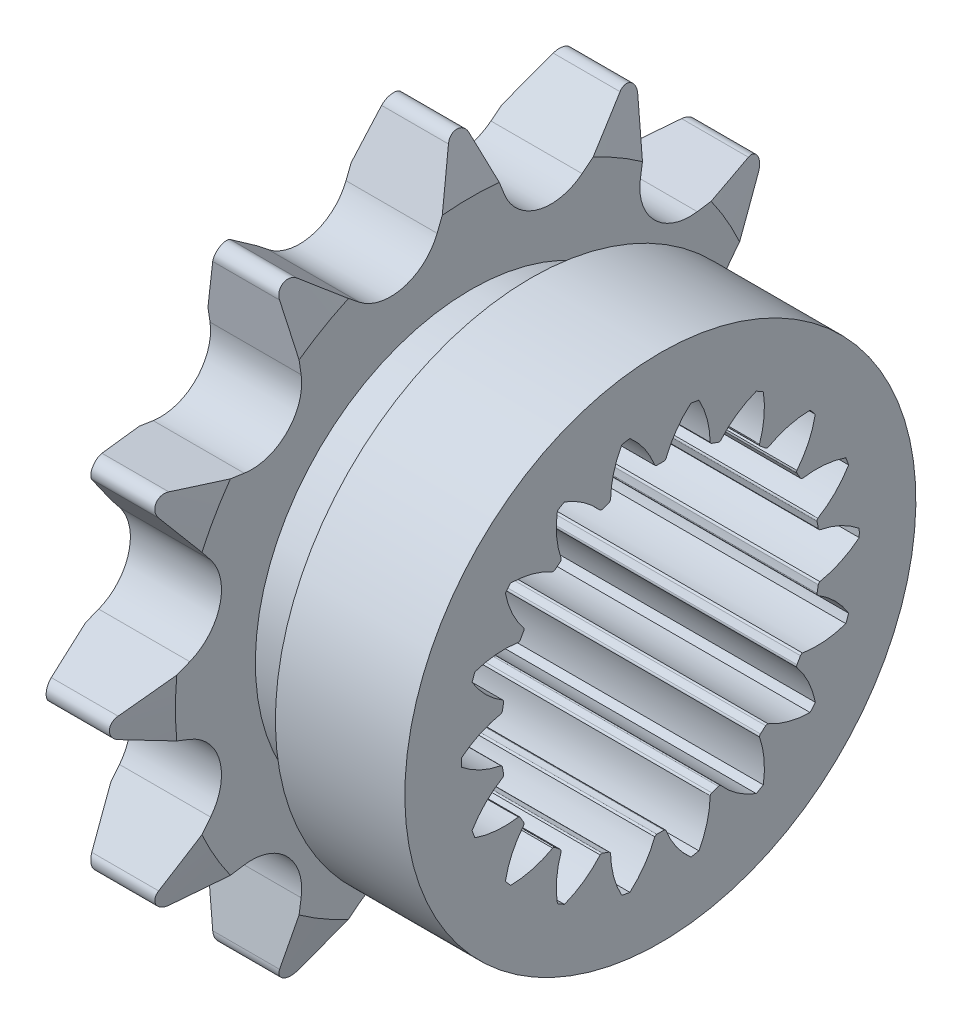
SolidWorks part; units mm, degrees
material "1144"
ref_plane "Front Plane" through (0, 0, 0) normal (0, 0, 1) x (1, 0, 0)
ref_plane "Top Plane" through (0, 0, 0) normal (0, 1, 0) x (1, 0, 0)
ref_plane "Right Plane" through (0, 0, 0) normal (1, 0, 0) x (0, 0, -1)
ref_axis "Axis1" through (-63.0158, 0, 0) along (1, 0, 0)
sketch "Sketch1" plane through (0, 0, 0) normal (0, 0, 1) x (1, 0, 0)
  line L0 (3.6068, 17.0561) -> (3.6068, 0) construction
  line L1 (22.225, 0) -> (22.225, 20.2311)
  line L3 (7.2136, 17.0561) -> (0, 17.0561)
  line L7 (0, 27.5082) -> (0, 30.0482) construction
  line L8 (0, 27.5082) -> (7.2136, 27.5082)
  line L9 (22.225, 0) -> (0, 0)
  line L10 (0, 0) -> (-84.1773, 0) construction
  line L11 (0, 17.0561) -> (0, 27.5082) construction
  line L12 (7.2136, 27.5082) -> (73.2462, 27.5082) construction
  line L13 (22.225, 0) -> (22.225, -20.2311) construction
  line L14 (3.6068, 0) -> (3.6068, -17.0561)
  line L15 (-15.4432, -17.0561) -> (22.6568, -17.0561)
  point P11 (0, 30.0482)
  dimension "D1" = 2.54
  dimension "hub_dia" = 40.4622
  dimension "width_teetth" = 7.2136
  dimension "D2" = 38.1
  dimension "length_thru" = 22.225
  dimension "OD" = 55.0164
  dimension "length_over_teeth" = 7.2136
  dimension "recess_hub_diam" = 34.1122
  dimension "hub_type" = 22.225
  dimension "projection 1" = 15.0114
  dimension "projection 2" = 0
sketch "Sketch2" plane through (0, 0, 0) normal (1, 0, 0) x (0, 0, -1)
  line L0 (0, 0) -> (0, 27.5082) construction
  line L1 (0, 0) -> (-13.7541, 23.8228) construction
  line L2 (0, 0) -> (-6.3502, 23.6991) construction
  line L3 (-0.8057, 26.9597) -> (-2.6638, 22.246)
  line L4 (-2.6638, 22.246) -> (-6.3502, 23.6991) construction
  line L5 (-0.8217, 27.4959) -> (0, 0) construction
  line L6 (-2.735, 27.3719) -> (0, 0) construction
  line L7 (-6.3502, 23.6991) -> (-2.4074, 24.0931) construction
  arc A1 (0, 27.5082) -> (-13.7541, 23.8228) centre (0, 0) ccw
  circle A2 centre (0, 0) radius 24.5351 construction
  circle A3 centre (-6.3502, 23.6991) radius 3.9624
  arc A4 (0, 27.5082) -> (-0.8057, 26.9597) centre (0, 26.6421) ccw
  dimension "pitch_diam" = 49.0703
  dimension "roller_diam" = 7.9248
  dimension "D1" = 1.712
  dimension "ang_1" = 30
  dimension "OD/2" = 27.5082
sketch "Taper Per Foot" plane through (0, 0, 0) normal (0, 0, 1) x (1, 0, 0)
  line L0 (22.225, 0) -> (22.225, 127)
  line L1 (22.225, 0) -> (22.225, 20.2311) construction
  line L2 (22.225, 127) -> (-282.575, 6.35)
  line L3 (-282.575, 6.35) -> (-282.575, 0)
  line L4 (-282.575, 0) -> (22.225, 0)
  line L5 (-282.575, 0) -> (-285.7823, 0) construction
  line L6 (-282.575, 6.35) -> (22.225, 6.35)
  line L7 (22.225, 6.35) -> (22.225, 127)
  dimension "1 Ft" = 304.8
  dimension "1 in" = 254
  dimension "Small End Diam" = 12.7
  dimension "Large End Diam" = 12.7
ref_plane "Plane1" through (7.2136, 0, 0) normal (1, 0, 0) x (0, 0, -1)
ref_plane "Plane2" through (7.2136, 0, 0) normal (1, 0, 0) x (0, 0, -1)
ref_plane "Plane3" through (0, 17.0561, 0) normal (-1, 0, 0) x (0, 0, 1)
ref_plane "Plane4" through (22.225, 0, 0) normal (1, 0, 0) x (0, 0, -1)
ref_plane "Plane5" through (3.6068, 0, 0) normal (1, 0, 0) x (0, 0, -1)
sketch "Sketch13" plane through (0, 0, 0) normal (0, 0, 1) x (1, 0, 0)
  line L0 (22.225, 0) -> (22.225, 20.2311) construction
  line L1 (0, 0) -> (22.225, 0)
  line L2 (0, 0) -> (0, 27.5082)
  line L3 (0, 27.5082) -> (22.225, 27.5082)
  line L4 (22.225, 0) -> (22.225, 27.5082)
revolve "Revolve1" add sketch "Sketch13" angle 360 about L10
sketch "Sketch6" plane through (0, -16.51, 0) normal (1, 0, 0) x (0, 0, -1)
  line L0 (-0.8057, 43.4697) -> (-2.6638, 38.756) construction
  line L1 (-0.8057, 43.4697) -> (-2.6638, 38.756)
  line L2 (-6.3502, 40.2091) -> (0, 16.51) construction
  line L3 (-12.7821, 40.2607) -> (-8.8161, 37.1075)
  arc A0 (0, 44.0182) -> (-0.8057, 43.4697) centre (0, 43.1521) ccw construction
  arc A1 (0, 44.0182) -> (-0.8057, 43.4697) centre (0, 43.1521) ccw
  arc A2 (-13.7541, 40.3328) -> (-12.7821, 40.2607) centre (-13.3211, 39.5828) cw
  arc A3 (-2.6638, 38.756) -> (-8.8161, 37.1075) centre (-6.3502, 40.2091) cw
  arc A4 (0, 44.0182) -> (-13.7541, 40.3328) centre (0, 16.51) ccw
extrude "Cut-Extrude1" cut sketch "Sketch6" along normal up to vertex (7.2136 mm away) up to point (7.2136, 17.0561, 0)
pattern_circular "CirPattern1" count 12 over 360 about axis through (-63.0158, 0, 0) along (1, 0, 0) of "Cut-Extrude1"
sketch "Sketch15" plane through (0, 0, 0) normal (0, 0, 1) x (1, 0, 0)
  line L1 (134.2136, 20.2311) -> (7.2136, 20.2311)
  line L2 (134.2136, 20.2311) -> (134.2136, 42.7482)
  line L3 (134.2136, 42.7482) -> (7.2136, 42.7482)
  line L4 (7.2136, 20.2311) -> (7.2136, 42.7482)
  line L5 (3.6068, 216.4797) -> (3.6068, 17.0561) construction
  line L6 (-127, 20.2311) -> (0, 20.2311)
  line L7 (0, 20.2311) -> (0, 42.7482)
  line L8 (-127, 42.7482) -> (0, 42.7482)
  line L9 (-127, 20.2311) -> (-127, 42.7482)
  dimension "D1" = 12.7
  dimension "D2" = 127
revolve "hub Cut-Revolve3" cut sketch "Sketch15" angle 360 about L10
sketch "Sketch4" plane through (0, 0, 0) normal (0, 0, 1) x (1, 0, 0)
  line L0 (0, 27.5082) -> (1.1045, 27.5082)
  line L2 (1.1045, 27.5082) -> (0, 23.3861)
  line L4 (0, 23.3861) -> (0, 27.5082)
  line L5 (3.6068, 27.5082) -> (3.6068, 44.9612) construction
  line L6 (7.2136, 27.5082) -> (6.1091, 27.5082)
  line L7 (7.2136, 23.3861) -> (7.2136, 27.5082)
  line L8 (6.1091, 27.5082) -> (7.2136, 23.3861)
  line L9 (0, 0) -> (-52.1231, 0) construction
  line L10 (0, 0) -> (-84.1773, 0) construction
  line L17 (0, 27.5082) -> (7.2136, 27.5082) construction
  dimension "D1" = 15
  dimension "D2" = 4.1221
revolve "Teeth Chamfer" cut sketch "Sketch4" angle 360 about L9
sketch "Sketch16" plane through (0, 0, 0) normal (0, 0, 1) x (1, 0, 0)
  line L1 (7.2136, 20.2311) -> (11.9761, 20.2311)
  line L2 (7.2136, 20.2311) -> (7.2136, 17.0561)
  line L3 (7.2136, 17.0561) -> (11.9761, 17.0561)
  line L4 (11.9761, 20.2311) -> (11.9761, 17.0561)
  line L5 (11.9761, 20.2311) -> (22.225, 20.2311) construction
  dimension "recess_width" = 4.7625
  dimension "recess_height" = 3.175
revolve "Recess" cut sketch "Sketch16" angle 360 about L10
sketch "Sketch32" plane through (22.225, 0, 0) normal (1, 0, 0) x (0, 0, -1)
  circle A1 centre (0, 0) radius 20.2311
  circle A2 centre (0, 0) radius 20.2311
  dimension "D1" = 0
extrude "Collar Reduction" [suppressed] cut sketch "Sketch32" against normal offset from surface (2.455 mm away) 19.77 up to face at (0, 0, 0)
ref_plane "Sprocket Teeth Center" through (3.6068, 0, 0) normal (-1, 0, 0) x (0, 0, 1)
sketch "Sketch35" plane through (3.6068, 0, 0) normal (1, 0, 0) x (0, 0, -1)
  circle A0 centre (0, 0) radius 24.5351 construction
  circle A1 centre (0, 0) radius 24.5351 construction
sketch "Sketch36" plane through (0, 0, 0) normal (-1, 0, 0) x (0, 0, 1)
  arc A34 (-7.5926, 13.7968) -> (-4.773, 11.8201) centre (-10.1337, 7.1728) cw
  arc A35 (-4.773, 11.8201) -> (-4.5847, 11.7902) centre (-4.6432, 12.0297) ccw
  arc A36 (-0.6644, 3.068) -> (-0.7894, 2.924) centre (-0.8986, 3.1451) cw
  arc A37 (-4.5847, 11.7902) -> (-4.0582, 11.9816) centre (0, 0) cw
  arc A38 (-8.1521, 13.4738) -> (-7.5639, 13.8125) centre (0, 0) cw
  arc A39 (-8.3407, 9.5111) -> (-7.9114, 9.8711) centre (0, 0) cw
  arc A40 (-7.85, 10.0436) -> (-7.9183, 9.8655) centre (-8.0965, 10.0359) cw
  arc A41 (-8.1521, 13.4738) -> (-7.85, 10.0436) centre (-1.145, 12.3625) ccw
  arc A42 (-2.4159, 15.5616) -> (-0.4424, 12.7398) centre (-7.0693, 10.2062) cw
  arc A43 (-0.4424, 12.7398) -> (-0.2757, 12.6472) centre (-0.2487, 12.8923) ccw
  arc A44 (-0.2757, 12.6472) -> (0.2845, 12.647) centre (0, 0) cw
  arc A45 (-3.0522, 15.4494) -> (-2.3836, 15.5666) centre (0, 0) cw
  arc A46 (-4.5847, 11.7902) -> (-4.0582, 11.9816) centre (0, 0) cw
  arc A47 (-3.9415, 12.1228) -> (-4.0666, 11.9788) centre (-4.1757, 12.1999) cw
  arc A48 (-3.0522, 15.4494) -> (-3.9415, 12.1228) centre (3.1523, 12.0085) ccw
  arc A49 (3.0522, 15.4494) -> (3.9415, 12.1228) centre (-3.1523, 12.0085) cw
  arc A50 (3.9415, 12.1228) -> (4.0666, 11.9788) centre (4.1757, 12.1999) ccw
  arc A51 (4.0666, 11.9788) -> (4.5929, 11.787) centre (0, 0) cw
  arc A52 (2.4159, 15.5616) -> (3.0842, 15.443) centre (0, 0) cw
  arc A53 (-0.2757, 12.6472) -> (0.2845, 12.647) centre (0, 0) cw
  arc A54 (0.4424, 12.7398) -> (0.2757, 12.6472) centre (0.2487, 12.8923) cw
  arc A55 (2.4159, 15.5616) -> (0.4424, 12.7398) centre (7.0693, 10.2062) ccw
  arc A56 (8.1521, 13.4738) -> (7.85, 10.0436) centre (1.145, 12.3625) cw
  arc A57 (7.85, 10.0436) -> (7.9183, 9.8655) centre (8.0965, 10.0359) ccw
  arc A58 (7.9183, 9.8655) -> (8.3473, 9.5053) centre (0, 0) cw
  arc A59 (7.5926, 13.7968) -> (8.18, 13.4568) centre (0, 0) cw
  arc A60 (4.0666, 11.9788) -> (4.5929, 11.787) centre (0, 0) cw
  arc A61 (4.773, 11.8201) -> (4.5847, 11.7902) centre (4.6432, 12.0297) cw
  arc A62 (7.5926, 13.7968) -> (4.773, 11.8201) centre (10.1337, 7.1728) ccw
  arc A63 (12.2688, 9.873) -> (10.8117, 6.753) centre (5.3042, 11.2253) cw
  arc A64 (10.8117, 6.753) -> (10.815, 6.5624) centre (11.0407, 6.6616) ccw
  arc A65 (10.815, 6.5624) -> (11.0949, 6.0771) centre (0, 0) cw
  arc A66 (11.8535, 10.368) -> (12.2892, 9.8476) centre (0, 0) cw
  arc A67 (7.9183, 9.8655) -> (8.3473, 9.5053) centre (0, 0) cw
  arc A68 (8.5279, 9.4748) -> (8.3407, 9.5111) centre (8.4775, 9.7162) cw
  arc A69 (11.8535, 10.368) -> (8.5279, 9.4748) centre (11.9758, 3.2743) ccw
  arc A70 (14.9057, 5.0814) -> (12.4694, 2.6479) centre (8.8236, 8.7342) cw
  arc A71 (12.4694, 2.6479) -> (12.4072, 2.4677) centre (12.6532, 2.4837) ccw
  arc A72 (12.4072, 2.4677) -> (12.5043, 1.916) centre (0, 0) cw
  arc A73 (14.6847, 5.6886) -> (14.9162, 5.0505) centre (0, 0) cw
  arc A74 (10.815, 6.5624) -> (11.0949, 6.0771) centre (0, 0) cw
  arc A75 (11.2542, 5.9867) -> (11.0907, 6.0849) centre (11.2894, 6.2307) cw
  arc A76 (14.6847, 5.6886) -> (11.2542, 5.9867) centre (12.3735, -1.0191) ccw
  arc A77 (15.7447, -0.3231) -> (12.623, -1.7765) centre (11.2787, 5.1896) cw
  arc A78 (12.623, -1.7765) -> (12.503, -1.9247) centre (12.7396, -1.9938) ccw
  arc A79 (12.503, -1.9247) -> (12.4055, -2.4763) centre (0, 0) cw
  arc A80 (15.7447, 0.3231) -> (15.744, -0.3557) centre (0, 0) cw
  arc A81 (12.4072, 2.4677) -> (12.5043, 1.916) centre (0, 0) cw
  arc A82 (12.623, 1.7765) -> (12.503, 1.9247) centre (12.7396, 1.9938) cw
  arc A83 (15.7447, 0.3231) -> (12.623, 1.7765) centre (11.2787, -5.1896) ccw
  arc A84 (14.6847, -5.6886) -> (11.2542, -5.9867) centre (12.3735, 1.0191) cw
  arc A85 (11.2542, -5.9867) -> (11.0907, -6.0849) centre (11.2894, -6.2307) ccw
  arc A86 (11.0907, -6.0849) -> (10.8104, -6.5699) centre (0, 0) cw
  arc A87 (14.9057, -5.0814) -> (14.6728, -5.719) centre (0, 0) cw
  arc A88 (12.503, -1.9247) -> (12.4055, -2.4763) centre (0, 0) cw
  arc A89 (12.4694, -2.6479) -> (12.4072, -2.4677) centre (12.6532, -2.4837) cw
  arc A90 (14.9057, -5.0814) -> (12.4694, -2.6479) centre (8.8236, -8.7342) ccw
  arc A91 (11.8535, -10.368) -> (8.5279, -9.4748) centre (11.9758, -3.2743) cw
  arc A92 (8.5279, -9.4748) -> (8.3407, -9.5111) centre (8.4775, -9.7162) ccw
  arc A93 (8.3407, -9.5111) -> (7.9114, -9.8711) centre (0, 0) cw
  arc A94 (12.2688, -9.873) -> (11.832, -10.3925) centre (0, 0) cw
  arc A95 (11.0907, -6.0849) -> (10.8104, -6.5699) centre (0, 0) cw
  arc A96 (10.8117, -6.753) -> (10.815, -6.5624) centre (11.0407, -6.6616) cw
  arc A97 (12.2688, -9.873) -> (10.8117, -6.753) centre (5.3042, -11.2253) ccw
  arc A98 (7.5926, -13.7968) -> (4.773, -11.8201) centre (10.1337, -7.1728) cw
  arc A99 (4.773, -11.8201) -> (4.5847, -11.7902) centre (4.6432, -12.0297) ccw
  arc A100 (4.5847, -11.7902) -> (4.0582, -11.9816) centre (0, 0) cw
  arc A101 (8.1521, -13.4738) -> (7.5639, -13.8125) centre (0, 0) cw
  arc A102 (8.3407, -9.5111) -> (7.9114, -9.8711) centre (0, 0) cw
  arc A103 (7.85, -10.0436) -> (7.9183, -9.8655) centre (8.0965, -10.0359) cw
  arc A104 (8.1521, -13.4738) -> (7.85, -10.0436) centre (1.145, -12.3625) ccw
  arc A105 (2.4159, -15.5616) -> (0.4424, -12.7398) centre (7.0693, -10.2062) cw
  arc A106 (0.4424, -12.7398) -> (0.2757, -12.6472) centre (0.2487, -12.8923) ccw
  arc A107 (0.2757, -12.6472) -> (-0.2845, -12.647) centre (0, 0) cw
  arc A108 (3.0522, -15.4494) -> (2.3836, -15.5666) centre (0, 0) cw
  arc A109 (4.5847, -11.7902) -> (4.0582, -11.9816) centre (0, 0) cw
  arc A110 (3.9415, -12.1228) -> (4.0666, -11.9788) centre (4.1757, -12.1999) cw
  arc A111 (3.0522, -15.4494) -> (3.9415, -12.1228) centre (-3.1523, -12.0085) ccw
  arc A112 (-3.0522, -15.4494) -> (-3.9415, -12.1228) centre (3.1523, -12.0085) cw
  arc A113 (-3.9415, -12.1228) -> (-4.0666, -11.9788) centre (-4.1757, -12.1999) ccw
  arc A114 (-4.0666, -11.9788) -> (-4.5929, -11.787) centre (0, 0) cw
  arc A115 (-2.4159, -15.5616) -> (-3.0842, -15.443) centre (0, 0) cw
  arc A116 (0.2757, -12.6472) -> (-0.2845, -12.647) centre (0, 0) cw
  arc A117 (-0.4424, -12.7398) -> (-0.2757, -12.6472) centre (-0.2487, -12.8923) cw
  arc A118 (-2.4159, -15.5616) -> (-0.4424, -12.7398) centre (-7.0693, -10.2062) ccw
  arc A119 (-8.1521, -13.4738) -> (-7.85, -10.0436) centre (-1.145, -12.3625) cw
  arc A120 (-7.85, -10.0436) -> (-7.9183, -9.8655) centre (-8.0965, -10.0359) ccw
  arc A121 (-7.9183, -9.8655) -> (-8.3473, -9.5053) centre (0, 0) cw
  arc A122 (-7.5926, -13.7968) -> (-8.18, -13.4568) centre (0, 0) cw
  arc A123 (-4.0666, -11.9788) -> (-4.5929, -11.787) centre (0, 0) cw
  arc A124 (-4.773, -11.8201) -> (-4.5847, -11.7902) centre (-4.6432, -12.0297) cw
  arc A125 (-7.5926, -13.7968) -> (-4.773, -11.8201) centre (-10.1337, -7.1728) ccw
  arc A126 (-12.2688, -9.873) -> (-10.8117, -6.753) centre (-5.3042, -11.2253) cw
  arc A127 (-10.8117, -6.753) -> (-10.815, -6.5624) centre (-11.0407, -6.6616) ccw
  arc A128 (-10.815, -6.5624) -> (-11.0949, -6.0771) centre (0, 0) cw
  arc A129 (-11.8535, -10.368) -> (-12.2892, -9.8476) centre (0, 0) cw
  arc A130 (-7.9183, -9.8655) -> (-8.3473, -9.5053) centre (0, 0) cw
  arc A131 (-8.5279, -9.4748) -> (-8.3407, -9.5111) centre (-8.4775, -9.7162) cw
  arc A132 (-11.8535, -10.368) -> (-8.5279, -9.4748) centre (-11.9758, -3.2743) ccw
  arc A133 (-14.9057, -5.0814) -> (-12.4694, -2.6479) centre (-8.8236, -8.7342) cw
  arc A134 (-12.4694, -2.6479) -> (-12.4072, -2.4677) centre (-12.6532, -2.4837) ccw
  arc A135 (-12.4072, -2.4677) -> (-12.5043, -1.916) centre (0, 0) cw
  arc A136 (-14.6847, -5.6886) -> (-14.9162, -5.0505) centre (0, 0) cw
  arc A137 (-10.815, -6.5624) -> (-11.0949, -6.0771) centre (0, 0) cw
  arc A138 (-11.2542, -5.9867) -> (-11.0907, -6.0849) centre (-11.2894, -6.2307) cw
  arc A139 (-14.6847, -5.6886) -> (-11.2542, -5.9867) centre (-12.3735, 1.0191) ccw
  arc A140 (-15.7447, 0.3231) -> (-12.623, 1.7765) centre (-11.2787, -5.1896) cw
  arc A141 (-12.623, 1.7765) -> (-12.503, 1.9247) centre (-12.7396, 1.9938) ccw
  arc A142 (-12.503, 1.9247) -> (-12.4055, 2.4763) centre (0, 0) cw
  arc A143 (-15.7447, -0.3231) -> (-15.744, 0.3557) centre (0, 0) cw
  arc A144 (-12.4072, -2.4677) -> (-12.5043, -1.916) centre (0, 0) cw
  arc A145 (-12.623, -1.7765) -> (-12.503, -1.9247) centre (-12.7396, -1.9938) cw
  arc A146 (-15.7447, -0.3231) -> (-12.623, -1.7765) centre (-11.2787, 5.1896) ccw
  arc A147 (-14.6847, 5.6886) -> (-11.2542, 5.9867) centre (-12.3735, -1.0191) cw
  arc A148 (-11.2542, 5.9867) -> (-11.0907, 6.0849) centre (-11.2894, 6.2307) ccw
  arc A149 (-11.0907, 6.0849) -> (-10.8104, 6.5699) centre (0, 0) cw
  arc A150 (-14.9057, 5.0814) -> (-14.6728, 5.719) centre (0, 0) cw
  arc A151 (-12.503, 1.9247) -> (-12.4055, 2.4763) centre (0, 0) cw
  arc A152 (-12.4694, 2.6479) -> (-12.4072, 2.4677) centre (-12.6532, 2.4837) cw
  arc A153 (-14.9057, 5.0814) -> (-12.4694, 2.6479) centre (-8.8236, 8.7342) ccw
  arc A154 (-11.8535, 10.368) -> (-8.5279, 9.4748) centre (-11.9758, 3.2743) cw
  arc A155 (-8.5279, 9.4748) -> (-8.3407, 9.5111) centre (-8.4775, 9.7162) ccw
  arc A156 (-8.3407, 9.5111) -> (-7.9114, 9.8711) centre (0, 0) cw
  arc A157 (-12.2688, 9.873) -> (-11.832, 10.3925) centre (0, 0) cw
  arc A158 (-11.0907, 6.0849) -> (-10.8104, 6.5699) centre (0, 0) cw
  arc A159 (-10.8117, 6.753) -> (-10.815, 6.5624) centre (-11.0407, 6.6616) cw
  arc A160 (-12.2688, 9.873) -> (-10.8117, 6.753) centre (-5.3042, 11.2253) ccw
  point P6 (-8.1521, 13.4738)
  point P24 (-3.1758, 15.7377)
  point P38 (2.2923, 15.8499)
  point P52 (7.469, 14.0851)
  point P66 (11.7299, 10.6563)
  point P81 (14.5611, 5.9769)
  point P95 (15.6211, 0.6114)
  point P109 (14.7821, -4.7931)
  point P123 (12.1452, -9.5847)
  point P137 (8.0286, -13.1855)
  point P151 (2.9286, -15.1611)
  point P165 (-2.5394, -15.2733)
  point P179 (-7.7161, -13.5085)
  point P193 (-11.977, -10.0797)
  point P207 (-14.8082, -5.4003)
  point P221 (-15.8682, -0.0348)
  point P235 (-15.0292, 5.3697)
  point P248 (-12.3924, 10.1613)
  point P258 (-0.1236, 0.2883)
  point P259 (0, 0)
extrude "Cut-Extrude2" cut sketch "Sketch36" against normal through all contours A157 A160 A159 A149 A148 A147 A150 A153 A152 A142 A141 A140 A143 A146 A145 A135 A134 A133 A136 A139 A138 A128 A127 A126 A129 A132 A131 A121 A120 A119 A122 A125 A124 A114 A113 A112 region at (0, 0, 0)
ref_axis "Axis2" through (22.225, 0, 0) along (-1, 0, 0)
